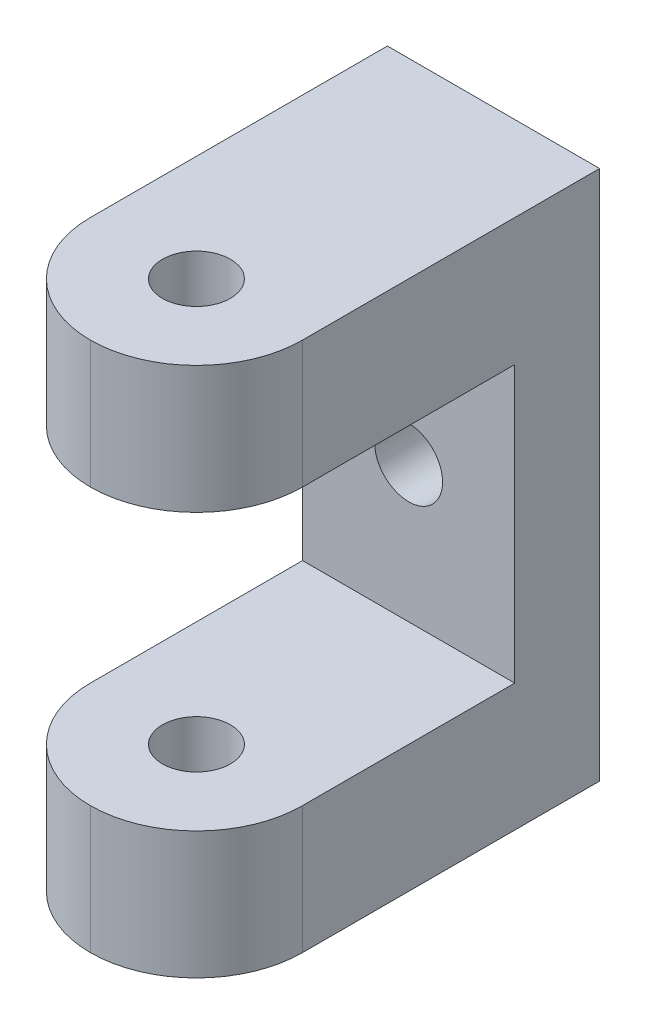
SolidWorks part; units mm, degrees
material "PET"
ref_plane "Front Plane" through (0, 0, 0) normal (0, 0, 1) x (1, 0, 0)
ref_plane "Top Plane" through (0, 0, 0) normal (0, 1, 0) x (1, 0, 0)
ref_plane "Right Plane" through (0, 0, 0) normal (1, 0, 0) x (0, 0, -1)
sketch "Sketch1" plane through (0, 0, 0) normal (0, 0, 1) x (1, 0, 0)
  line L1 (0, 0) -> (10, 0)
  line L2 (0, 0) -> (0, 6)
  line L3 (0, 6) -> (10, 6)
  line L4 (10, 0) -> (10, 6)
  line L5 (0, 19) -> (10, 19)
  line L6 (0, 19) -> (0, 25)
  line L7 (0, 25) -> (10, 25)
  line L8 (10, 19) -> (10, 25)
  dimension "D1" = 6
  dimension "D2" = 25
  dimension "D3" = 10
extrude "Boss-Extrude1" add sketch "Sketch1" along normal blind 15
fillet "Fillet1" radius 5 2 edges at (10, 22, 15) (0, 22, 15)
fillet "Fillet2" radius 5 2 edges at (10, 3, 15) (0, 3, 15)
sketch "Sketch2" plane through (0, 0, 0) normal (0, 0, -1) x (-1, 0, 0)
  line L1 (-10, 25) -> (0, 25)
  line L2 (-10, 25) -> (-10, 0)
  line L3 (-10, 0) -> (0, 0)
  line L4 (0, 25) -> (0, 0)
extrude "Boss-Extrude2" add sketch "Sketch2" along normal blind 4
sketch "Sketch3" plane through (0, 25, 0) normal (0, 1, 0) x (1, 0, 0)
  circle A0 centre (5, -10) radius 1.6
  dimension "D1" = 3.2
extrude "Cut-Extrude1" cut sketch "Sketch3" against normal through all
sketch "Sketch4" plane through (0, 0, -4) normal (0, 0, -1) x (-1, 0, 0)
  circle A0 centre (-5, 12.5) radius 1.6
  dimension "D1" = 3.2
extrude "Cut-Extrude2" cut sketch "Sketch4" against normal up to next
